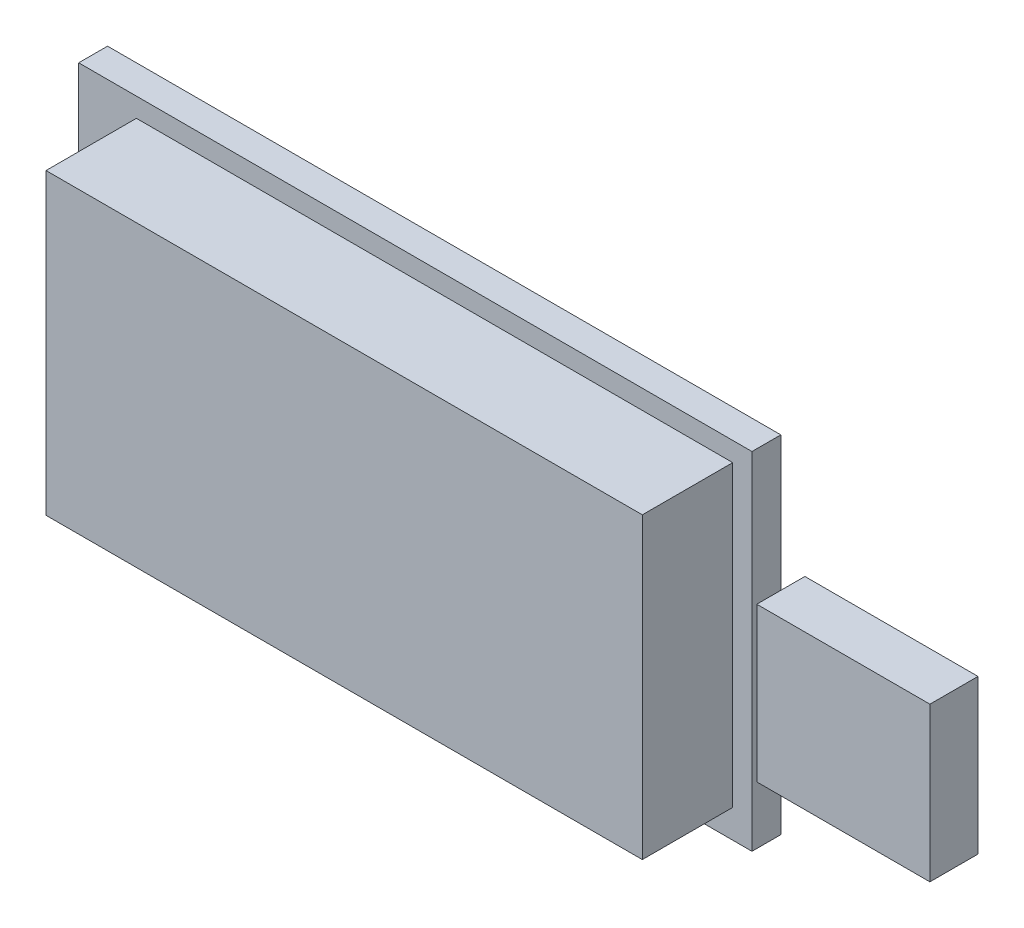
SolidWorks part; units mm, degrees
ref_plane "Plano frontal" through (0, 0, 0) normal (0, 0, 1) x (1, 0, 0)
ref_plane "Plano superior" through (0, 0, 0) normal (0, 1, 0) x (1, 0, 0)
ref_plane "Plano direito" through (0, 0, 0) normal (1, 0, 0) x (0, 0, -1)
sketch "Esboço1" plane through (0, 0, 0) normal (0, 0, 1) x (1, 0, 0)
  line L1 (0, 0) -> (35, 0)
  line L2 (0, 0) -> (0, 18)
  line L3 (0, 18) -> (35, 18)
  line L4 (35, 0) -> (35, 18)
  line L5 (35, 3) -> (44, 3)
  line L6 (44, 3) -> (44, 11)
  line L7 (44, 11) -> (35, 11)
  line L8 (34, 9) -> (34, 17)
  line L9 (34, 17) -> (3, 17)
  line L10 (3, 17) -> (3, 1.4773)
  line L11 (3, 1.4773) -> (34, 1.4773)
  line L12 (34, 1.4773) -> (34, 9)
extrude "Ressalto-extrusão1" add sketch "Esboço1" along normal blind 1.5 contours L1 L4 L3 L2 L12 L11 L10 L9 L8 region at (0.3936, 9, 0)
extrude "Ressalto-extrusão2" add sketch "Esboço1<3>" along normal blind 6.2 contours L11 L12 L8 L9 L10 region at (18.5, 9.2387, 0)
sketch "Esboço1<3>" plane through (0, 0, 0) normal (0, 0, 1) x (1, 0, 0) same geometry as "Esboço1"
extrude "Ressalto-extrusão3" add sketch "Esboço1<4>" along normal mid plane 2.5 contours L6 L7 L4 L5 region at (39.5, 7, 0)
sketch "Esboço1<4>" plane through (0, 0, 0) normal (0, 0, 1) x (1, 0, 0) same geometry as "Esboço1"
